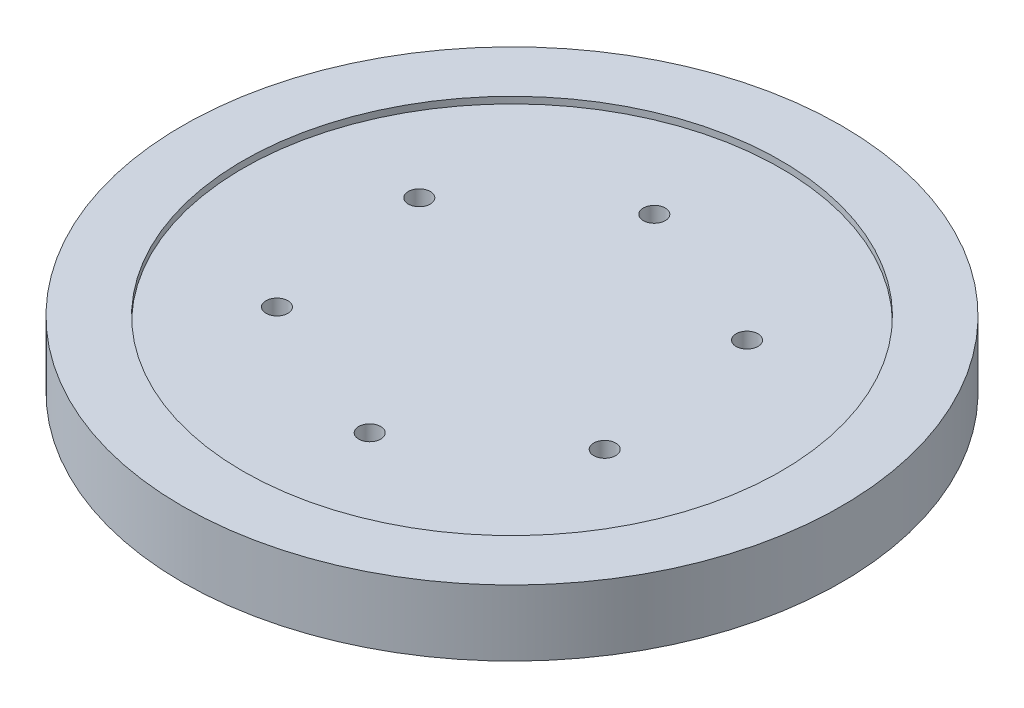
SolidWorks part; units mm, degrees
ref_plane "Alzado" through (0, 0, 0) normal (0, 0, 1) x (1, 0, 0)
ref_plane "Planta" through (0, 0, 0) normal (0, 1, 0) x (1, 0, 0)
ref_plane "Vista lateral" through (0, 0, 0) normal (1, 0, 0) x (0, 0, -1)
sketch "Croquis1" plane through (0, 0, 0) normal (0, 1, 0) x (1, 0, 0)
  circle A0 centre (0, 0) radius 75
  circle A1 centre (0, 0) radius 61.225
  dimension "D1" = 150
  dimension "D2" = 122.45
extrude "Saliente-Extruir1" add sketch "Croquis1" along normal blind 15 contours A1 | A0 A1 region at (-72.8787, 0, 0) region at (0, 0, 0)
extrude "Cortar-Extruir3" cut sketch "Croquis1<4>" against normal blind 1.5 from surface flip side to cut starting at face at (0, 15, 75)
sketch "Croquis1<4>" plane through (0, 0, 0) normal (0, 1, 0) x (1, 0, 0) same geometry as "Croquis1"
sketch "Croquis2" plane through (0, 13.5, 0) normal (0, 1, 0) x (1, 0, 0)
  circle A4 centre (-35.3382, 14.2415) radius 2.5
  circle A5 centre (-5.3356, 37.7245) radius 2.5
  circle A6 centre (30.0026, 23.4831) radius 2.5
  circle A7 centre (35.3382, -14.2415) radius 2.5
  circle A8 centre (5.3356, -37.7245) radius 2.5
  circle A9 centre (-30.0026, -23.4831) radius 2.5
  circle A10 centre (-35.3382, 14.2415) radius 4.25
  circle A11 centre (-4.027, 36.0223) radius 4.25
  circle A12 centre (30.4914, 19.7964) radius 4.25
  circle A13 centre (33.6985, -18.2103) radius 4.25
  circle A14 centre (2.3873, -39.9912) radius 4.25
  circle A15 centre (-32.1311, -23.7653) radius 4.25
  point P29 (-0.8199, -1.9844)
  dimension "D1" = 8.5
  dimension "D2" = 6
extrude "Cortar-Extruir5" cut sketch "Croquis2" against normal through all both and the other way through all contours A8 | A7 | A6 | A5 | A4 | A9
extrude "Cortar-Extruir6" cut sketch "Croquis2<4>" along normal blind 5.2 and the other way through all from surface contours A13 | A12 | A11 | A10 | A15 | A14 starting at face at (5.3356, 0, 40.2245)
sketch "Croquis2<4>" plane through (0, 13.5, 0) normal (0, 1, 0) x (1, 0, 0) same geometry as "Croquis2"
sketch "Croquis3" plane through (0, 0, 0) normal (0, -1, 0) x (1, 0, 0)
  circle A0 centre (35.0406, 53.5552) radius 2.5
  circle A1 centre (-53.5552, 35.0406) radius 2.5
  circle A2 centre (53.5552, -35.0406) radius 2.5
  circle A3 centre (-35.0406, -53.5552) radius 2.5
  dimension "D1" = 5
extrude "Cortar-Extruir7" cut sketch "Croquis3" against normal blind 10
